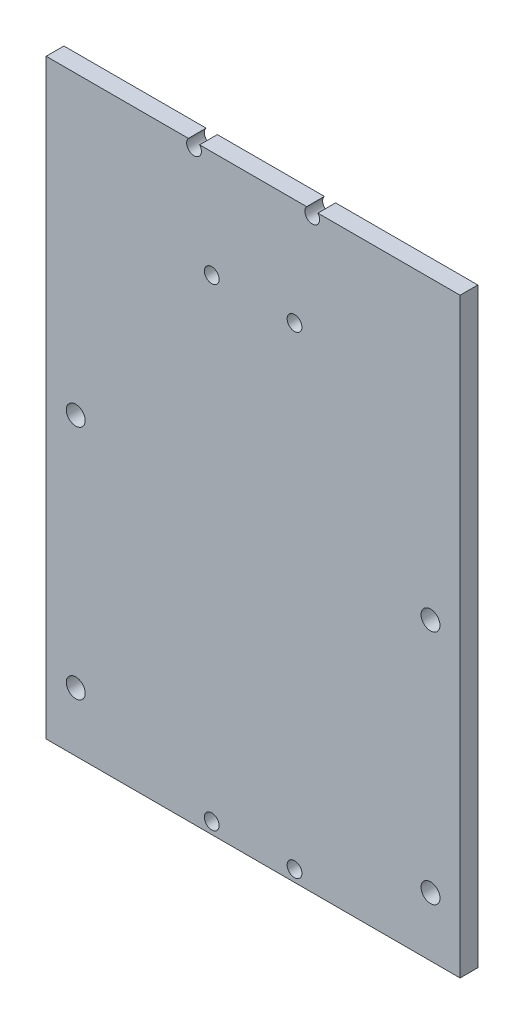
SolidWorks part; units mm, degrees
ref_plane "前视基准面" through (0, 0, 0) normal (0, 0, 1) x (1, 0, 0)
ref_plane "上视基准面" through (0, 0, 0) normal (0, 1, 0) x (1, 0, 0)
ref_plane "右视基准面" through (0, 0, 0) normal (1, 0, 0) x (0, 0, -1)
sketch "草图1" plane through (0, 0, 0) normal (0, 0, 1) x (1, 0, 0)
  line L1 (-79.2332, 22.3507) -> (-9.2332, 22.3507)
  line L2 (-79.2332, 22.3507) -> (-79.2332, 122.3507)
  line L3 (-79.2332, 122.3507) -> (-9.2332, 122.3507)
  line L4 (-9.2332, 22.3507) -> (-9.2332, 122.3507)
  dimension "D1" = 70
  dimension "D2" = 100
extrude "凸台-拉伸1" add sketch "草图1" along normal blind 3
sketch "草图2" plane through (0, 0, 3) normal (0, 0, 1) x (1, 0, 0)
  circle A2 centre (-74.2332, 32.3507) radius 1.6
  circle A3 centre (-14.2332, 32.3507) radius 1.6
  circle A4 centre (-14.2332, 72.2862) radius 1.6
  circle A5 centre (-74.2332, 72.2862) radius 1.6
extrude "切除-拉伸1" cut sketch "草图2" against normal blind 3
sketch "草图3" plane through (0, 0, 0) normal (0, 0, -1) x (-1, 0, 0)
  circle A0 centre (37.2331, 104.2862) radius 1.25
  circle A1 centre (51.2331, 104.2862) radius 1.25
  circle A2 centre (37.2331, 24.2862) radius 1.25
  circle A3 centre (51.2331, 24.2862) radius 1.25
  circle A4 centre (34.2332, 121.5362) radius 1.25
  circle A5 centre (54.2332, 121.5362) radius 1.25
  dimension "D1" = 2.5
extrude "切除-拉伸2" cut sketch "草图3" against normal blind 3
